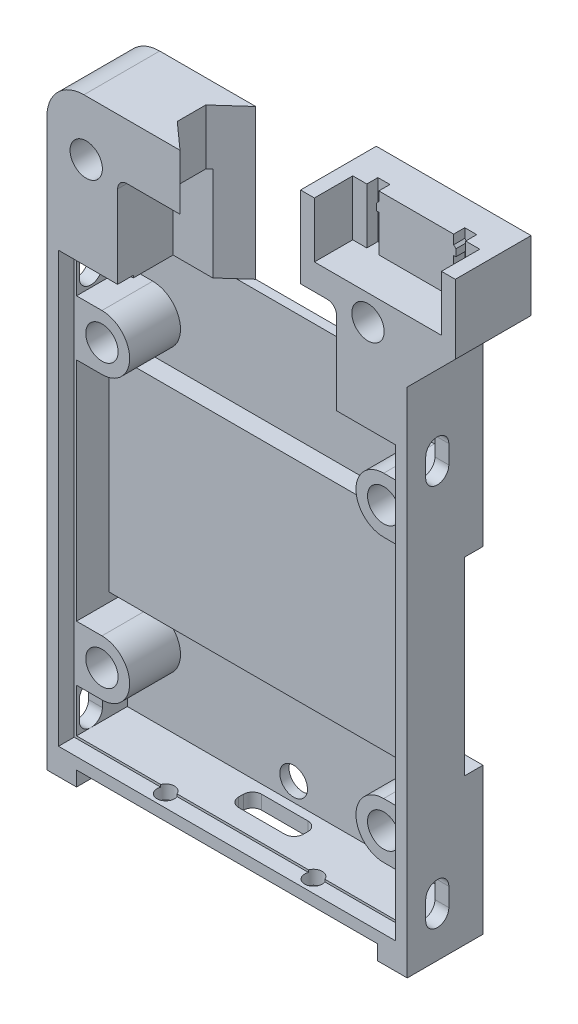
SolidWorks part; units mm, degrees
ref_plane "Front Plane" through (0, 0, 0) normal (0, 0, 1) x (1, 0, 0)
ref_plane "Top Plane" through (0, 0, 0) normal (0, 1, 0) x (1, 0, 0)
ref_plane "Right Plane" through (0, 0, 0) normal (1, 0, 0) x (0, 0, -1)
sketch "Sketch1" plane through (0, 0, 0) normal (0, 0, 1) x (1, 0, 0)
  line L0 (15.25, -20.35) -> (18, -20.35)
  line L1 (-19.5, -32.6) -> (19.5, -32.6)
  line L2 (-19.5, -32.6) -> (-19.5, 31.1)
  line L3 (-19.5, 31.1) -> (19.5, 31.1)
  line L4 (19.5, -32.6) -> (19.5, 31.1)
  line L5 (-15.25, -20.35) -> (-18, -20.35)
  line L6 (15.25, -26.35) -> (18, -26.35)
  line L7 (6.95, 31.1) -> (-15.5, 31.1) construction
  line L8 (-18, -31.1) -> (-18, 29.6)
  line L9 (-18, 29.6) -> (18, 29.6)
  line L10 (18, -31.1) -> (18, 29.6)
  line L11 (-18, -31.1) -> (18, -31.1)
  line L12 (-18, 14.9) -> (18, 14.9)
  line L13 (7.85, 14.9) -> (-4.95, 14.9) construction
  line L14 (-15.25, 4.15) -> (-18, 4.15)
  line L15 (-15.25, 10.15) -> (-18, 10.15)
  line L16 (15.25, 10.15) -> (18, 10.15)
  line L17 (15.25, 4.15) -> (18, 4.15)
  line L18 (-15.25, -26.35) -> (-18, -26.35)
  line L19 (19.5, -34.2) -> (19.5, -18.35) construction
  line L20 (-19.5, -34.2) -> (-19.5, -18.35) construction
  line L21 (15.3, -32.6) -> (-15.3, -32.6) construction
  line L22 (0, 31.1) -> (0, -32.6) construction
  line L23 (9.45, 26.9) -> (24.7, 26.9)
  line L24 (9.45, 26.9) -> (9.45, 33.9)
  line L25 (9.45, 33.9) -> (24.7, 33.9)
  line L26 (24.7, 26.9) -> (24.7, 33.9)
  line L27 (18, 29.6) -> (19.5, 31.1) construction
  line L28 (18.75, 30.35) -> (0, 30.35) construction
  line L29 (9.45, 26.9) -> (7.95, 26.9) construction
  line L30 (-7.95, 31.1) -> (7.95, 31.1)
  line L31 (-7.95, 31.1) -> (-7.95, 29.6)
  line L32 (-7.95, 29.6) -> (7.95, 29.6)
  line L33 (7.95, 31.1) -> (7.95, 29.6)
  line L34 (-7.95, 31.1) -> (7.95, 29.6) construction
  line L35 (-7.95, 29.6) -> (7.95, 31.1) construction
  line L36 (7.95, 26.9) -> (7.95, 29.6) construction
  line L37 (18, 29.6) -> (19.5, 29.6) construction
  line L38 (24.7, 26.4) -> (19.5, 21.2)
  line L39 (9.45, 33.9) -> (7.95, 33.9)
  line L40 (23.2, 33.9) -> (23.2, 26.9)
  line L41 (7.95, 33.9) -> (7.95, 31.1)
  line L42 (24.7, 30.4) -> (23.2, 30.4) construction
  line L43 (24.7, 26.9) -> (19.5, 26.9)
  line L44 (24.7, 26.9) -> (24.7, 26.4)
  line L45 (24.7, 26.4) -> (19.5, 26.4)
  line L46 (19.5, 26.9) -> (19.5, 26.4)
  circle A0 centre (15.25, -23.35) radius 1.75
  arc A1 (-15.5, 31.1) -> (-19.5, 27.1) centre (-15.5, 27.1) ccw construction
  circle A2 centre (15.25, -23.35) radius 3
  arc A3 (-15.5, 31.1) -> (-19.5, 27.1) centre (-15.5, 27.1) ccw
  arc A4 (-15.5, 29.6) -> (-18, 27.1) centre (-15.5, 27.1) ccw
  circle A6 centre (-15.25, -23.35) radius 1.75
  circle A7 centre (-15.25, -23.35) radius 1.75
  circle A8 centre (-15.25, 7.15) radius 1.75
  circle A9 centre (15.25, 7.15) radius 1.75
  circle A10 centre (15.25, 25.15) radius 1.75
  circle A11 centre (-15.25, 25.15) radius 1.75
  circle A12 centre (-15.25, -23.35) radius 3
  circle A13 centre (-15.25, -23.35) radius 3
  circle A14 centre (15.25, 7.15) radius 3
  circle A15 centre (-15.25, 7.15) radius 3
  dimension "D2" = 1.5
  dimension "D4" = 6
  dimension "D3" = 3.5
  dimension "D5" = 13.75
  dimension "D6" = 15.9
  dimension "D7" = 7
  dimension "D8" = 45
  dimension "D9" = 0.5
  dimension "D1" = 1.5
extrude "Base shape" add sketch "Sketch1" along normal up to surface (8.2 mm away) contours A15 L8 L9 L31 L3 A3 L2 L1 L4 L23 L10 A14 A2 L11 A12 | A12 L8 L18 | A12 L8 A6 | L8 A12 | A12 L5 L8 | A15 L8 L14 | A15 L8 A8 | L8 A15 | A15 L15 L8 | L23 A10 L24 L9 A4 L8 L12 L10 A11 | A4 L9 L8 | L33 L3 L31 L9 | L3 L33 L9 L24 | L24 L9 L10 L23 L4 L3 | L24 L23 L10 L9 | A14 L10 L16 | L10 A14 A9 | A14 L17 L10 | L10 A14 | L10 A2 L6 | A2 L10 A0 | L0 A2 L10 | A2 L10 | L40 L25 L24 L3 L4 L23 | L25 L40 L23 L26 | L38 L45 L4 | L45 L44 L23 L4 | L39 L41 L3 L24 region at (16.8481, -20.9099, 0) region at (17.3601, -20.8437, 0) region at (18.7469, -8.1, 0) region at (17.3601, -25.8563, 0) region at (18.1004, -23.35, 0) region at (17.3601, 4.6437, 0) region at (16.8481, 4.7099, 0) region at (18.1004, 7.15, 0) region at (17.3601, 9.6563, 0) region at (-17.3601, -25.8563, 0) region at (-0.6044, 21.831, 0) region at (-18.1004, -23.35, 0) region at (-17.9169, -23.35, 0) region at (13.725, 28.25, 0) region at (15.3803, 29.9053, 0) region at (-17.3601, -20.8437, 0) region at (22.1, 26.65, 0) region at (17.77, 31.4935, 0) region at (-17.3601, 9.6563, 0) region at (-17.4416, 29.0416, 0) region at (8.7, 30.35, 0) region at (21.2333, 24.6667, 0) region at (23.95, 30.4, 0) region at (-16.8481, 9.5901, 0) region at (-18.1004, 7.15, 0) region at (-17.3601, 4.6437, 0) region at (0, 30.35, 0) region at (8.7, 32.5, 0)
sketch "Sketch3" plane through (19.5, 0, 0) normal (1, 0, 0) x (0, 0, -1)
  line L1 (0, -18.35) -> (-2, -18.35)
  line L2 (0, -18.35) -> (0, 2.15)
  line L3 (0, 2.15) -> (-2, 2.15)
  line L4 (-2, -18.35) -> (-2, 2.15)
  line L5 (0, -18.35) -> (1.75, -18.35) construction
  line L6 (0, 2.15) -> (1.75, 2.15) construction
  line L7 (0, -32.6) -> (0, 21.2) construction
  dimension "D1" = 2
extrude "Strap cut" cut sketch "Sketch3" against normal through all
sketch "Sketch4" plane through (0, 31.1, 0) normal (0, 1, 0) x (1, 0, 0)
  line L2 (7.95, 0) -> (-5.0998, 0)
  line L4 (-15.5, 0) -> (7.95, 0) construction
  line L5 (-15.5, -8.2) -> (7.95, -8.2) construction
  line L6 (7.95, -8.2) -> (-5.0998, -8.2)
  line L12 (7.95, -8.3) -> (7.95, 0.1)
  line L13 (7.95, 0.1) -> (-4.9883, 0.1)
  line L14 (-4.9883, 0.1) -> (-7.95, -2.5553)
  line L15 (-7.95, -2.5553) -> (-7.95, -5.6447)
  line L16 (-7.95, -5.6447) -> (-4.9883, -8.3)
  line L17 (-4.9883, -8.3) -> (7.95, -8.3)
  line L18 (7.95, -8.3) -> (7.95, 0.1)
  line L19 (7.95, 0.1) -> (-4.9883, 0.1)
  line L20 (-4.9883, 0.1) -> (-7.95, -2.5553)
  line L21 (-7.95, -2.5553) -> (-7.95, -5.6447)
  line L22 (-7.95, -5.6447) -> (-4.9883, -8.3)
  line L23 (-4.9883, -8.3) -> (7.95, -8.3)
  dimension "D1" = 0.1
extrude "XT60 cut" cut sketch "Sketch4" against normal up to next contours L21 L22 L18 L20 region at (0.4142, 31.1, 4.1)
sketch "Sketch6" plane through (0, 0, 8.2) normal (0, 0, 1) x (1, 0, 0)
  line L0 (8.85, 14.9) -> (10.85, 14.9) construction
  line L1 (11.85, 24.1) -> (11.85, 15.9) construction
  line L3 (-11.85, 14.9) -> (11.85, 14.9)
  line L4 (-11.85, 24.1) -> (-11.85, 15.9) construction
  line L5 (11.85, 24.1) -> (11.85, 15.9)
  line L6 (10.85, 25.1) -> (-10.85, 25.1)
  line L7 (-11.85, 24.1) -> (-11.85, 15.9)
  line L8 (-11.85, 15.9) -> (-11.85, 14.9)
  line L9 (11.85, 15.9) -> (11.85, 14.9)
  arc A2 (-10.85, 25.1) -> (-11.85, 24.1) centre (-10.85, 24.1) ccw construction
  arc A3 (-10.85, 25.1) -> (-11.85, 24.1) centre (-10.85, 24.1) ccw
  arc A4 (11.85, 24.1) -> (10.85, 25.1) centre (10.85, 24.1) ccw construction
  arc A5 (11.85, 24.1) -> (10.85, 25.1) centre (10.85, 24.1) ccw
  line M1 (7.95, 33.9) -> (7.95, 14.9)
  line M15 (-5.0998, 14.9) -> (-5.0998, 31.1)
  line M118 (7.95, 14.9) -> (18, 14.9)
  line M134 (-18, 14.9) -> (-5.0998, 14.9)
extrude "IO wires cut" cut sketch "Sketch6" against normal blind 6 contours L7 L8 M134 M15 | L3 M15 M1 | L5 L9 M1 M118 region at (-8.465, 19.9848, 8.2) region at (1.4251, 20, 8.2) region at (9.8906, 19.9735, 8.2)
sketch "Sketch7" plane through (-18, 0, 0) normal (1, 0, 0) x (0, 0, -1)
  line L6 (0, -18.35) -> (0, -20.35)
  line L7 (-2, -18.35) -> (0, -18.35)
  line L8 (-2, 2.15) -> (-2, -18.35)
  line L9 (0, 2.15) -> (-2, 2.15)
  line L12 (0, 3.15) -> (-3, 3.15)
  line L13 (-3, 3.15) -> (-3, -19.35)
  line L14 (-3, -19.35) -> (-1, -19.35)
  line L15 (-1, -19.35) -> (-1, -20.35)
  line L16 (-1, -20.35) -> (0, -20.35)
  line L17 (0, 3.15) -> (-1, 3.15)
  line L19 (0, -31.1) -> (-1, -31.1)
  line L22 (0, -31.1) -> (0, -20.35)
  line L23 (0, -20.35) -> (-1, -20.35)
  line L24 (-1, -31.1) -> (-1, -20.35)
  line L25 (0, 3.15) -> (0, 14.9)
  line L26 (0, 14.9) -> (-1, 14.9)
  line L27 (-1, 3.15) -> (-1, 14.9)
  line L28 (-8.2, 14.9) -> (0, 14.9) construction
  line L31 (0, -20.35) -> (0, -18.35) construction
  line L32 (0, 2.15) -> (-2, 2.15) construction
  line M48 (0, -20.35) -> (0, -18.35)
  line M49 (0, -18.35) -> (-2, -18.35)
  line M50 (-2, -18.35) -> (-2, 2.15)
  line M51 (-2, 2.15) -> (0, 2.15)
  line M52 (0, 2.15) -> (0, 4.15)
  line M53 (0, 4.15) -> (-8.2, 4.15)
  line M55 (-8.2, -20.35) -> (0, -20.35)
  dimension "D1" = 1
extrude "Bottom" add sketch "Sketch7" along normal up to surface (36 mm away) contours L27 L25 L26 M53 | L27 L12 M52 M53 | L14 L15 L12 L13 M55 M48 M49 M50 M51 M52 | L24 L19 L22 M55 region at (-18, -8.5273, 2.2091) region at (-18, -25.725, 0.5) region at (-18, 3.65, 0.5) region at (-18, 9.525, 0.5) up to face at (18, -8.1, 2.55)
sketch "Sketch9" plane through (0, 0, 0) normal (0, 0, -1) x (-1, 0, 0)
  circle A0 centre (15.25, -23.35) radius 1.75 construction
  circle A1 centre (-15.25, 7.15) radius 1.75 construction
  circle A2 centre (15.25, 7.15) radius 1.75 construction
  circle A3 centre (15.25, -23.35) radius 1.75 construction
  circle A4 centre (15.25, -23.35) radius 1.75
  circle A5 centre (-15.25, 7.15) radius 1.75
  circle A6 centre (15.25, 7.15) radius 1.75
  circle A7 centre (15.25, -23.35) radius 1.75
  circle A8 centre (-15.25, -23.35) radius 1.75 construction
  circle A9 centre (-15.25, -23.35) radius 1.75
extrude "Bottom holes" cut sketch "Sketch9" against normal up to next contours A5 | A6 | A4 | A9 region at (-15.25, -23.35, 0) region at (15.25, 7.15, 0) region at (-15.25, 7.15, 0) region at (15.25, -23.35, 0)
sketch "Sketch5" plane through (19.5, 0, 0) normal (1, 0, 0) x (0, 0, -1)
  line L1 (-8.2, -32.6) -> (-8.2, 21.2) construction
  line L2 (-6.2, -31.1) -> (-3.7, -31.1)
  line L3 (-6.2, -31.1) -> (-6.2, -26.6)
  line L4 (-6.2, -26.6) -> (-3.7, -26.6)
  line L5 (-3.7, -31.1) -> (-3.7, -26.6)
  line L6 (-8.2, -31.1) -> (-1, -31.1) construction
  line L7 (-8.2, 14.9) -> (-1, 14.9) construction
  line L8 (-6.2, 14.9) -> (-3.7, 14.9)
  line L9 (-6.2, 14.9) -> (-6.2, 10.4)
  line L10 (-6.2, 10.4) -> (-3.7, 10.4)
  line L11 (-3.7, 14.9) -> (-3.7, 10.4)
  line L14 (-4.95, -26.6) -> (-4.95, -31.1) construction
  line L15 (-4.95, 14.9) -> (-4.95, 10.4) construction
  circle A0 centre (-4.95, -27.85) radius 1.25
  circle A1 centre (-4.95, -29.85) radius 1.25
  circle A2 centre (-4.95, 13.65) radius 1.25
  circle A3 centre (-4.95, 11.65) radius 1.25
  point P20 (-4.95, -29.1)
  point P31 (-4.95, 12.4)
  dimension "D3" = 4.5
  dimension "D1" = 2
  dimension "D2" = 2.5
extrude "Power wires cut" cut sketch "Sketch5" against normal through all contours A2 | A3 | A3 A2 L9 | A3 L11 A2 | A1 | A0 | A1 L5 A0 | A1 A0 L3 | A0 A1 | A2 A3 region at (19.5, -29.9662, 4.95) region at (19.5, -28.85, 6.057) region at (19.5, -28.85, 3.843) region at (19.5, -27.7338, 4.95) region at (19.5, -28.85, 4.95) region at (19.5, 13.7662, 4.95) region at (19.5, 12.65, 6.057) region at (19.5, 12.65, 3.843) region at (19.5, 11.5338, 4.95) region at (19.5, 12.65, 4.95)
sketch "Sketch8" plane through (0, 0, 8.2) normal (0, 0, 1) x (1, 0, 0)
  line L1 (-18, 14.9) -> (18, -31.1) construction
  line L3 (-18.25, -31.35) -> (18.25, -31.35)
  line L4 (-18.25, -31.35) -> (-18.25, 15.15)
  line L5 (-18.25, 15.15) -> (18.25, 15.15)
  line L6 (18.25, -31.35) -> (18.25, 15.15)
  line L7 (-18.25, -31.35) -> (18.25, 15.15) construction
  line L8 (-18.25, 15.15) -> (18.25, -31.35) construction
  line L10 (-18, 10.15) -> (-18, 14.9) construction
  line L11 (-18, 14.9) -> (-18.25, 14.9) construction
  line L12 (-18, 14.9) -> (-18, 15.15) construction
  point P2 (0, -8.1)
  dimension "D1" = 0.25
extrude "PCB cut" cut sketch "Sketch8" against normal blind 1.7
sketch "Sketch11" plane through (0, -32.6, 0) normal (0, -1, 0) x (1, 0, 0)
  line L0 (19.5, 8.2) -> (19.5, 0) construction
  line L1 (-19.5, 8.2) -> (19.5, 8.2)
  line L2 (-19.5, 8.2) -> (-19.5, -1.8)
  line L3 (-19.5, -1.8) -> (19.5, -1.8)
  line L4 (19.5, 8.2) -> (19.5, -1.8)
  line L5 (-19.5, 3.2) -> (19.5, 3.2) construction
  line L6 (0, -1.8) -> (0, 8.2) construction
  line L8 (-2.5, 4.45) -> (2.5, 4.45)
  line L9 (-3.5, 3.45) -> (-3.5, 2.95)
  line L10 (-2.5, 1.95) -> (2.5, 1.95)
  line L11 (3.5, 3.45) -> (3.5, 2.95)
  line L12 (-3.5, 4.45) -> (3.5, 1.95) construction
  line L13 (-3.5, 1.95) -> (3.5, 4.45) construction
  arc A0 (2.5, 4.45) -> (3.5, 3.45) centre (2.5, 3.45) cw
  arc A1 (2.5, 1.95) -> (3.5, 2.95) centre (2.5, 2.95) ccw
  arc A2 (-3.5, 2.95) -> (-2.5, 1.95) centre (-2.5, 2.95) ccw
  arc A3 (-2.5, 4.45) -> (-3.5, 3.45) centre (-2.5, 3.45) ccw
  point P11 (0, 3.2)
  dimension "D4" = 1
  dimension "D1" = 10
  dimension "D2" = 7
  dimension "D3" = 2.5
extrude "Ledbar wires cut" cut sketch "Sketch11" against normal up to next contours L8 A3 L9 A2 L10 A1 L11 A0 region at (0, -32.6, 3.2)
sketch "Sketch13" plane through (0, -32.6, 0) normal (0, -1, 0) x (1, 0, 0)
  line L0 (-19.5, 8.2) -> (19.5, 8.2) construction
  line L1 (19.5, 0) -> (16.3, 0)
  line L2 (19.5, 0) -> (19.5, 8.2)
  line L3 (19.5, 8.2) -> (16.3, 8.2)
  line L4 (16.3, 0) -> (16.3, 8.2)
  line L5 (16.1, -1.8) -> (16.1, 8.2) construction
  line L6 (0, 8.2) -> (0, 0) construction
  line L7 (-19.5, 0) -> (-16.3, 0)
  line L8 (-19.5, 0) -> (-19.5, 8.2)
  line L9 (-19.5, 8.2) -> (-16.3, 8.2)
  line L10 (-16.3, 0) -> (-16.3, 8.2)
  dimension "D1" = 0.2
extrude "Ledbar sides" add sketch "Sketch13" along normal blind 1.6
sketch "Sketch16" plane through (0, 33.9, 0) normal (0, 1, 0) x (1, 0, 0)
  line L0 (7.95, -6.125) -> (24.7, -6.125) construction
  line L1 (7.95, -8.2) -> (24.7, -8.2) construction
  line L2 (21.675, -2.85) -> (20.375, -2.85)
  line L3 (20.375, -4.05) -> (20.375, -2.85)
  line L4 (9.45, -4.05) -> (23.2, -4.05)
  line L5 (9.45, -4.05) -> (9.45, -8.2)
  line L6 (9.45, -8.2) -> (23.2, -8.2)
  line L7 (23.2, -4.05) -> (23.2, -8.2)
  line L8 (9.45, -4.05) -> (23.2, -8.2) construction
  line L9 (9.45, -8.2) -> (23.2, -4.05) construction
  line L10 (24.7, -8.2) -> (24.7, 0) construction
  line L11 (7.95, -8.2) -> (7.95, 0) construction
  line L12 (16.325, -8.2) -> (16.325, -4.05) construction
  line L13 (11.625, -2.85) -> (11.625, -4.05) construction
  line L14 (10.975, -4.05) -> (12.275, -4.05)
  line L15 (10.975, -4.05) -> (10.975, -2.85)
  line L16 (10.975, -2.85) -> (12.275, -2.85)
  line L17 (12.275, -4.05) -> (12.275, -2.85)
  line L18 (10.975, -2.85) -> (10.975, -8.2) construction
  line L19 (21.675, -4.05) -> (21.675, -2.85)
  point P6 (16.325, -6.125)
  dimension "D1" = 13.75
  dimension "D2" = 4.15
  dimension "D3" = 1.3
  dimension "D4" = 1.2
  dimension "D5" = 4.7
extrude "Balance plug cut" cut sketch "Sketch16" against normal blind 6 contours L7 L4 L5 L6 | L4 L17 L16 L15 | L4 L19 L2 L3 region at (21.025, 33.9, 3.45) region at (16.325, 33.9, 6.125) region at (11.625, 33.9, 3.45)
sketch "Sketch17" plane through (0, 0, 2.85) normal (0, 0, 1) x (1, 0, 0)
  line L0 (16.325, 33.9) -> (16.325, 27.9) construction
  line L1 (12.275, 33.9) -> (20.375, 33.9) construction
  line L2 (12.275, 27.9) -> (20.375, 27.9) construction
  line L3 (12.275, 27.9) -> (12.275, 33.9) construction
  line L4 (12.025, 32.9) -> (20.625, 32.9)
  line L5 (12.025, 32.9) -> (12.025, 31.9)
  line L6 (12.025, 31.9) -> (20.625, 31.9)
  line L7 (20.625, 32.9) -> (20.625, 31.9)
  line L8 (12.025, 32.9) -> (20.625, 31.9) construction
  line L9 (12.025, 31.9) -> (20.625, 32.9) construction
  line L10 (12.025, 32.65) -> (12.275, 32.9)
  line L11 (20.625, 32.65) -> (20.375, 32.9)
  point P6 (16.325, 32.4)
  line M7 (20.375, 33.9) -> (20.375, 27.9)
  dimension "D1" = 0.25
  dimension "D2" = 1
  dimension "D3" = 1
  dimension "D4" = 45
extrude "Balance plug locks" add sketch "Sketch17" along normal up to surface (1.2 mm away) contours L10 L5 L6 L4 M7 | L7 L11 L6 M7 region at (16.2154, 32.3984, 2.85) region at (20.494, 32.3405, 2.85) up to face at (16.325, 30.9, 4.05)
sketch "Sketch18" plane through (0, 0, 0) normal (0, 0, -1) x (-1, 0, 0)
  line L0 (0, -32.6) -> (0, -18.35) construction
  line L1 (16.3, -32.6) -> (-16.3, -32.6) construction
  line L2 (19.5, -18.35) -> (-19.5, -18.35) construction
  line L3 (-19.5, -30.6) -> (19.5, -30.6) construction
  line L4 (-19.5, -34.2) -> (-19.5, -18.35) construction
  line L5 (19.5, -34.2) -> (19.5, -18.35) construction
  circle A0 centre (0, -29.1) radius 1.5
  dimension "D2" = 3
  dimension "D1" = 2
extrude "PDB removal hole" cut sketch "Sketch18" against normal up to next
sketch "Sketch14" plane through (0, -32.6, 0) normal (0, -1, 0) x (1, 0, 0)
  circle A0 centre (8, 6.85) radius 0.95
  circle A1 centre (-8, 6.85) radius 0.95
  dimension "D1" = 1.9
extrude "Ledbar holes" cut sketch "Sketch14" against normal up to next
sketch "Sketch10" [suppressed] plane through (0, 0, 2) normal (0, 0, -1) x (-1, 0, 0)
  line L0 (0, 2.15) -> (0, -18.35) construction
  line L1 (19.5, 2.15) -> (-19.5, 2.15) construction
  line L2 (19.5, -18.35) -> (-19.5, -18.35) construction
  line L3 (19.5, 2.15) -> (19.5, -18.35) construction
  line L4 (-19.5, 1.15) -> (19.5, 1.15)
  line L5 (-19.5, 1.15) -> (-19.5, 0.65)
  line L6 (-19.5, 0.65) -> (19.5, 0.65)
  line L7 (19.5, 1.15) -> (19.5, 0.65)
  line L8 (-19.5, 1.15) -> (19.5, 0.65) construction
  line L9 (-19.5, 0.65) -> (19.5, 1.15) construction
  line L10 (-19.5, 2.15) -> (19.5, 2.15) construction
  line L11 (-19.5, -1.35) -> (19.5, -1.35)
  line L12 (19.5, -0.85) -> (19.5, -1.35)
  line L13 (-19.5, -0.85) -> (19.5, -0.85)
  line L14 (-19.5, -0.85) -> (-19.5, -1.35)
  line L15 (-19.5, -3.35) -> (19.5, -3.35)
  line L16 (19.5, -2.85) -> (19.5, -3.35)
  line L17 (-19.5, -2.85) -> (19.5, -2.85)
  line L18 (-19.5, -2.85) -> (-19.5, -3.35)
  line L19 (-19.5, -5.35) -> (19.5, -5.35)
  line L20 (19.5, -4.85) -> (19.5, -5.35)
  line L21 (-19.5, -4.85) -> (19.5, -4.85)
  line L22 (-19.5, -4.85) -> (-19.5, -5.35)
  line L23 (-19.5, -7.35) -> (19.5, -7.35)
  line L24 (19.5, -6.85) -> (19.5, -7.35)
  line L25 (-19.5, -6.85) -> (19.5, -6.85)
  line L26 (-19.5, -6.85) -> (-19.5, -7.35)
  line L27 (-19.5, -9.35) -> (19.5, -9.35)
  line L28 (19.5, -8.85) -> (19.5, -9.35)
  line L29 (-19.5, -8.85) -> (19.5, -8.85)
  line L30 (-19.5, -8.85) -> (-19.5, -9.35)
  line L31 (-19.5, -11.35) -> (19.5, -11.35)
  line L32 (19.5, -10.85) -> (19.5, -11.35)
  line L33 (-19.5, -10.85) -> (19.5, -10.85)
  line L34 (-19.5, -10.85) -> (-19.5, -11.35)
  line L35 (-19.5, -13.35) -> (19.5, -13.35)
  line L36 (19.5, -12.85) -> (19.5, -13.35)
  line L37 (-19.5, -12.85) -> (19.5, -12.85)
  line L38 (-19.5, -12.85) -> (-19.5, -13.35)
  line L39 (-19.5, -15.35) -> (19.5, -15.35)
  line L40 (19.5, -14.85) -> (19.5, -15.35)
  line L41 (-19.5, -14.85) -> (19.5, -14.85)
  line L42 (-19.5, -14.85) -> (-19.5, -15.35)
  line L43 (-19.5, -17.35) -> (19.5, -17.35)
  line L44 (19.5, -16.85) -> (19.5, -17.35)
  line L45 (-19.5, -16.85) -> (19.5, -16.85)
  line L46 (-19.5, -16.85) -> (-19.5, -17.35)
  point P6 (0, 0.9)
  dimension "D1" = 1
  dimension "D2" = 0.5
  dimension "D4" = 2
  dimension "D3" = 10
extrude "3D print ribs" [suppressed] add sketch "Sketch10" along normal up to surface (2 mm away) up to face at (-1.5, -29.1, 0)
